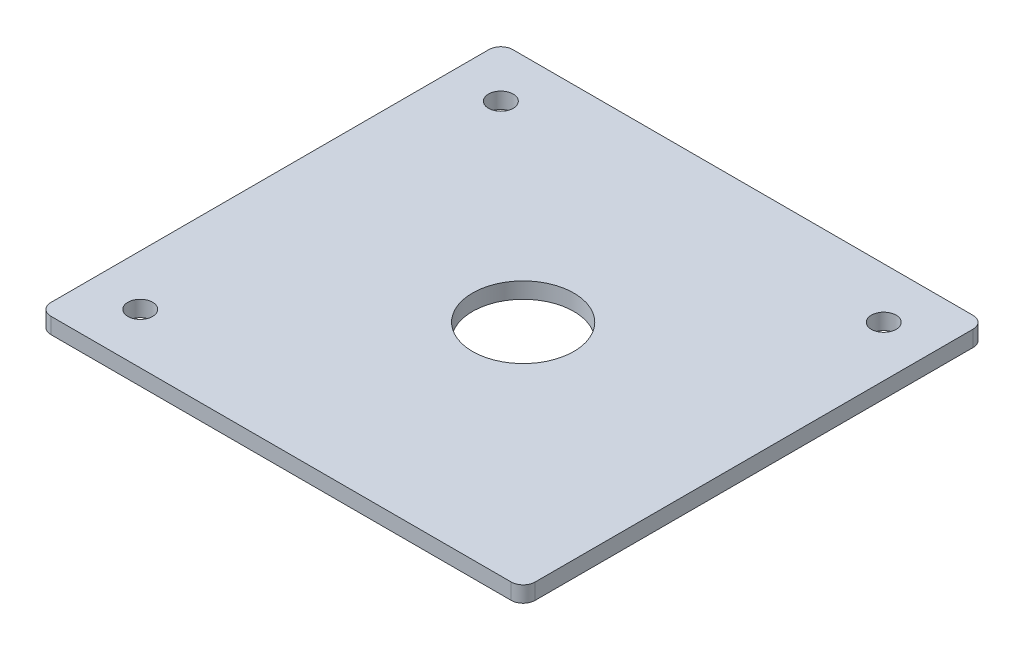
SolidWorks part; units mm, degrees
ref_plane "Front Plane" through (0, 0, 0) normal (0, 0, 1) x (1, 0, 0)
ref_plane "Top Plane" through (0, 0, 0) normal (0, 1, 0) x (1, 0, 0)
ref_plane "Right Plane" through (0, 0, 0) normal (1, 0, 0) x (0, 0, -1)
sketch "Sketch1" plane through (0, 0, 0) normal (0, 1, 0) x (1, 0, 0)
  line L0 (0.7175, -90.4) -> (88.7175, -90.4) construction
  line L1 (0.7175, 0) -> (122.1175, 0)
  line L2 (0.7175, 0) -> (0.7175, -115.8)
  line L3 (0.7175, -115.8) -> (122.1175, -115.8)
  line L4 (122.1175, 0) -> (122.1175, -115.8)
  line L5 (-27.2825, -90.4) -> (88.7175, -90.4) construction
  line L6 (88.7175, -90.4) -> (96.7175, -82.4) construction
  line L7 (96.7175, -82.4) -> (96.7175, -33.4) construction
  line L12 (96.7175, -33.4) -> (88.7175, -25.4) construction
  line L13 (88.7175, -25.4) -> (0.7175, -25.4) construction
  line L14 (88.7175, -25.4) -> (-27.2825, -25.4) construction
  line L15 (0.7175, -25.4) -> (0.7175, -90.4) construction
  line L16 (13.4175, -12.7) -> (0.7175, -12.7) construction
  line L17 (13.4175, -12.7) -> (13.4175, 0) construction
  line L18 (109.4175, -12.7) -> (109.4175, 0) construction
  line L19 (109.4175, -12.7) -> (122.1175, -12.7) construction
  line L20 (13.4175, -103.1) -> (0.7175, -103.1) construction
  line L21 (13.4175, -103.1) -> (13.4175, -100) construction
  line L22 (13.4175, -103.1) -> (13.4175, -115.8) construction
  line L23 (13.4175, -12.7) -> (16.5175, -12.7) construction
  line L25 (109.4175, -12.7) -> (109.4175, -15.8) construction
  circle A0 centre (64.2175, -57.9) radius 12.7
  circle A1 centre (13.4175, -12.7) radius 3.1
  circle A2 centre (109.4175, -12.7) radius 3.1
  circle A4 centre (13.4175, -103.1) radius 3.1
  dimension "D4" = 25.4
  dimension "D5" = 88
  dimension "D6" = 6.2
  dimension "D1" = 25.4
  dimension "D2" = 25.4
  dimension "D3" = 25.4
  dimension "D7" = 12.7
extrude "Boss-Extrude1" add sketch "Sketch1" along normal blind 4
fillet "Fillet1" radius 3 4 edges at (122.1175, 2, 0) (122.1175, 2, 115.8) (0.7175, 2, 115.8) (0.7175, 2, 0)
